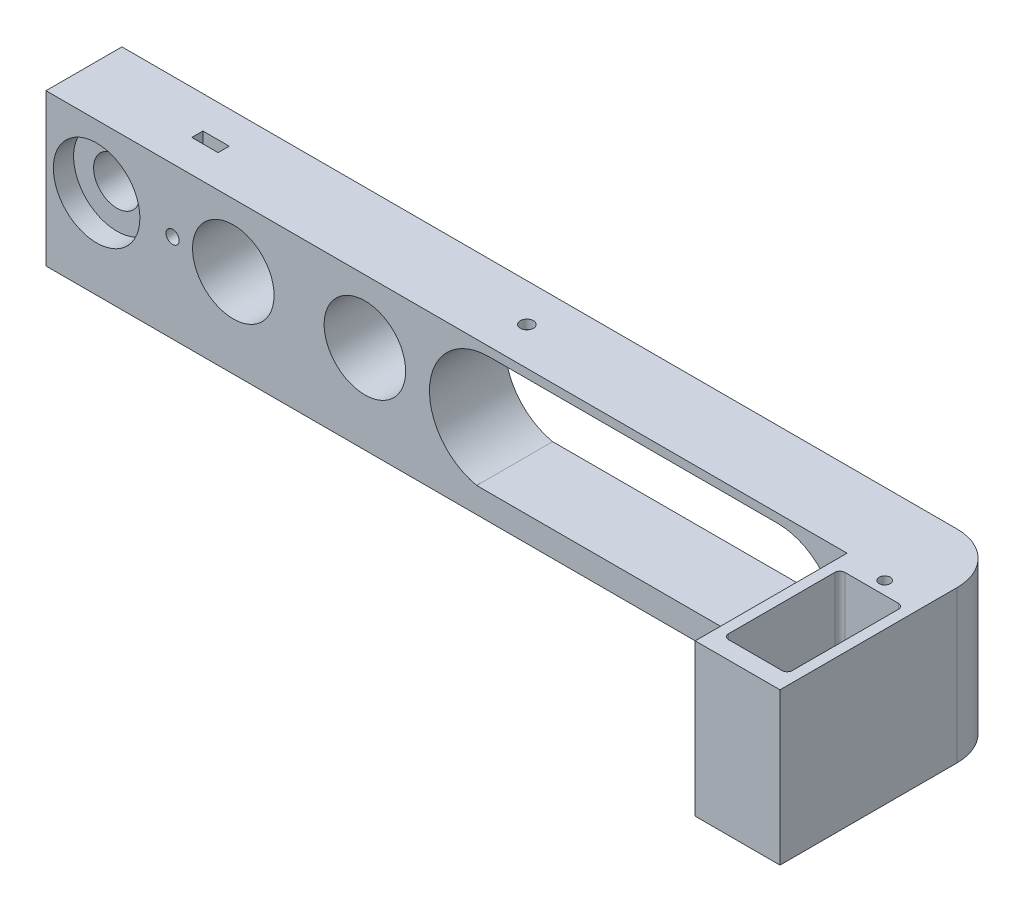
SolidWorks part; units mm, degrees
ref_plane "Front Plane" through (0, 0, 0) normal (0, 0, 1) x (1, 0, 0)
ref_plane "Top Plane" through (0, 0, 0) normal (0, 1, 0) x (1, 0, 0)
ref_plane "Right Plane" through (0, 0, 0) normal (1, 0, 0) x (0, 0, -1)
sketch "Sketch1" plane through (0, 0, 0) normal (0, 1, 0) x (1, 0, 0)
  line L1 (-87.5, -7.5) -> (87.5, -7.5)
  line L2 (-87.5, -7.5) -> (-87.5, 7.5)
  line L3 (-87.5, 7.5) -> (87.5, 7.5)
  line L4 (87.5, -7.5) -> (87.5, 7.5)
  line L5 (-87.5, -7.5) -> (87.5, 7.5) construction
  line L6 (-87.5, 7.5) -> (87.5, -7.5) construction
  point P0 (0, 0)
  dimension "D1" = 175
  dimension "D2" = 15
extrude "Boss-Extrude1" add sketch "Sketch1" along normal blind 25
sketch "Sketch3" plane through (0, 0, 7.5) normal (0, 0, 1) x (1, 0, 0)
  line L0 (-87.5, 25) -> (-87.5, 0) construction
  line L1 (-50.5, 12.5) -> (-24.5, 12.5) construction
  circle A1 centre (-77.5, 12.5) radius 8.55
  circle A2 centre (-77.5, 12.5) radius 4.6
  circle A3 centre (-50.5, 12.5) radius 8.05
  circle A4 centre (-24.5, 12.5) radius 8.05
  circle A5 centre (-62.5, 12.5) radius 1.3
  point P10 (-37.5, 12.5)
  point P16 (-87.5, 12.5)
  dimension "D1" = 17.1
  dimension "D2" = 9.2
  dimension "D3" = 16.1
  dimension "D4" = 9.9
  dimension "D5" = 2.6
  dimension "D6" = 10
  dimension "D7" = 15
  dimension "D8" = 25
extrude "Cut-Extrude1" cut sketch "Sketch3" against normal up to next contours A2 | A5 | A3 | A4 region at (-77.5, 12.5, 7.5) region at (-50.5, 12.5, 7.5) region at (-24.5, 12.5, 7.5) region at (-62.5, 12.5, 7.5)
extrude "Cut-Extrude2" cut sketch "Sketch3<3>" against normal blind 4 contours A1 A2 region at (-85.8082, 12.5, 7.5)
sketch "Sketch3<3>" plane through (0, 0, 7.5) normal (0, 0, 1) x (1, 0, 0) same geometry as "Sketch3"
sketch "Sketch4" plane through (0, 0, 0) normal (0, 0, 1) x (1, 0, 0)
  line L0 (-65.1, 14.0011) -> (-65.1, 25)
  line L1 (-62.5, 15.5022) -> (-65.1, 14.0011)
  line L2 (-65.1, 14.0011) -> (-65.1, 10.9989)
  line L3 (-65.1, 10.9989) -> (-62.5, 9.4978)
  line L4 (-62.5, 9.4978) -> (-59.9, 10.9989)
  line L5 (-59.9, 10.9989) -> (-59.9, 14.0011)
  line L6 (-59.9, 14.0011) -> (-62.5, 15.5022)
  line L7 (-87.5, 25) -> (87.5, 25) construction
  line L8 (-65.1, 25) -> (-59.9, 25)
  line L9 (-59.9, 25) -> (-59.9, 14.0011)
  circle A0 centre (-62.5, 12.5) radius 2.6 construction
  dimension "D1" = 5.2
extrude "Cut-Extrude3" cut sketch "Sketch4" against normal mid plane 2.2 contours L5 L6 L1 L2 L3 L4 | L9 L8 L0 L1 L6 region at (-62.5, 19.8667, 0) region at (-62.5, 12.5, 0)
sketch "Sketch5" plane through (0, 25, 0) normal (0, 1, 0) x (1, 0, 0)
  circle A0 centre (0, 0) radius 1.3
  dimension "D1" = 2.6
extrude "Cut-Extrude4" cut sketch "Sketch5" against normal up to next
sketch "Sketch6" plane through (0, 0, 7.5) normal (0, 0, 1) x (1, 0, 0)
  line L0 (0, 11.5) -> (57, 11.5) construction
  line L1 (0, 23) -> (57, 23)
  line L2 (0, 0) -> (57, 0)
  line L4 (28.5, 11.5) -> (28.5, -7.044) construction
  line L5 (0, 23.25) -> (57, 23.25)
  line L6 (0, -0.25) -> (57, -0.25)
  line L7 (0, 26.25) -> (57, 26.25)
  line L8 (0, -3.25) -> (57, -3.25)
  line L9 (-9.2365, 0) -> (66.2365, 0)
  line L10 (-87.5, 0) -> (87.5, 0) construction
  arc A0 (0, 23) -> (0, 0) centre (0, 11.5) ccw
  arc A1 (57, 0) -> (57, 23) centre (57, 11.5) ccw
  arc A2 (57, -0.25) -> (57, 23.25) centre (57, 11.5) ccw
  arc A3 (0, 23.25) -> (0, -0.25) centre (0, 11.5) ccw
  arc A4 (57, -3.25) -> (57, 26.25) centre (57, 11.5) ccw
  arc A5 (0, 26.25) -> (0, -3.25) centre (0, 11.5) ccw
  point P2 (28.5, 11.5)
  point P34 (0, 0)
  line M26 (-87.5, 0) -> (87.5, 0)
  dimension "D2" = 80
  dimension "D1" = 23
  dimension "D3" = 0.25
  dimension "D4" = 3
extrude "Cut-Extrude6" cut sketch "Sketch6" against normal up to next contours A1 L1 A0 M26 | L5 A3 L9 A0 L1 A1 A2 M26 region at (-11.5838, 11.5, 7.5) region at (28.5, 11.5, 7.5)
sketch "Sketch8" plane through (0, 0, 0) normal (0, -1, 0) x (1, 0, 0)
  line L1 (-87.5, 7.5) -> (87.5, 7.5)
  line L2 (-87.5, 7.5) -> (-87.5, -7.5)
  line L3 (-87.5, -7.5) -> (87.5, -7.5)
  line L4 (87.5, 7.5) -> (87.5, -7.5)
extrude "Boss-Extrude2" add sketch "Sketch8" along normal blind 5
sketch "Sketch9" plane through (0, 0, 7.5) normal (0, 0, 1) x (1, 0, 0)
  line L0 (87.5, -5) -> (-87.5, -5) construction
  line L1 (87.5, 25) -> (70.75, 25)
  line L2 (87.5, 25) -> (87.5, -5)
  line L3 (87.5, -5) -> (70.75, -5)
  line L4 (70.75, 25) -> (70.75, -5)
  arc A1 (59.4109, 0) -> (57, 23.25) centre (57, 11.5) ccw construction
  dimension "D1" = 2
extrude "Boss-Extrude3" add sketch "Sketch9" along normal blind 30
sketch "Sketch10" plane through (0, 25, 0) normal (0, 1, 0) x (1, 0, 0)
  line L0 (87.5, -37.5) -> (70.75, -37.5) construction
  line L1 (73.825, -34) -> (84.425, -34)
  line L2 (72.825, -33) -> (72.825, -12)
  line L3 (73.825, -11) -> (84.425, -11)
  line L4 (85.425, -33) -> (85.425, -12)
  line L5 (70.75, -37.5) -> (70.75, -7.5) construction
  arc A0 (73.825, -34) -> (72.825, -33) centre (73.825, -33) cw
  arc A1 (84.425, -34) -> (85.425, -33) centre (84.425, -33) ccw
  arc A2 (84.425, -11) -> (85.425, -12) centre (84.425, -12) cw
  arc A3 (72.825, -12) -> (73.825, -11) centre (73.825, -12) cw
  circle A4 centre (79.125, -8.45) radius 1.1
  point P6 (79.125, -37.5)
  point P7 (79.125, -34)
  point P9 (79.125, -11)
  point P12 (70.75, -22.5)
  point P13 (72.825, -22.5)
  point P20 (85.425, -11)
  point P23 (72.825, -11)
  dimension "D3" = 1
  dimension "D4" = 1.45
  dimension "D5" = 2.2
  dimension "D1" = 23
  dimension "D2" = 12.6
extrude "Cut-Extrude7" cut sketch "Sketch10" against normal blind 30
fillet "Fillet1" radius 10 1 edges at (87.5, 10, -7.5)
